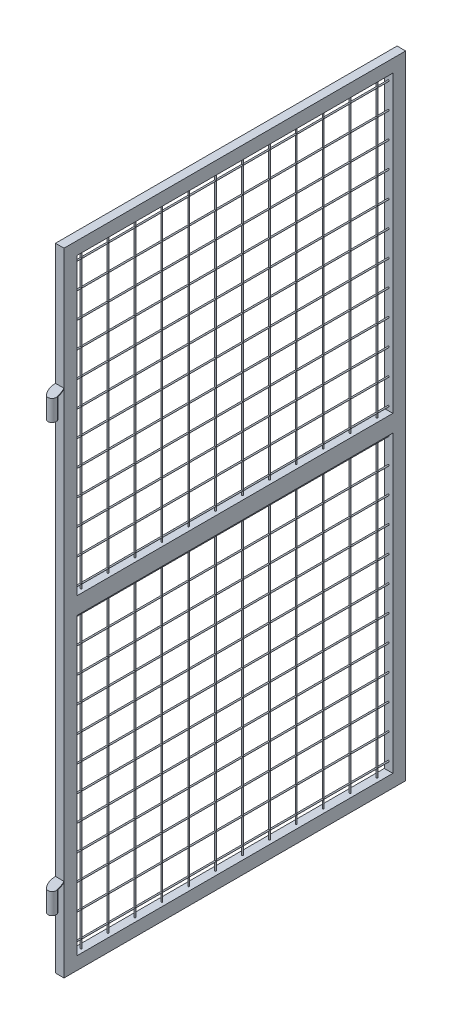
SolidWorks part; units mm, degrees
material "1.0570 (S355J2G3)"
ref_plane "Top Plane" through (0, 0, 0) normal (0, 0, 1) x (1, 0, 0)
ref_plane "Right Plane" through (0, 0, 0) normal (0, 1, 0) x (1, 0, 0)
ref_plane "Front Plane" through (0, 0, 0) normal (1, 0, 0) x (0, 0, -1)
sketch "Sketch1" plane through (0, 0, 0) normal (1, 0, 0) x (0, 0, -1)
  line L0 (30, 1450) -> (770, 1450)
  line L1 (0, 0) -> (800, 0)
  line L2 (0, 0) -> (0, 1480)
  line L3 (0, 1480) -> (800, 1480)
  line L4 (800, 0) -> (800, 1480)
  line L5 (770, 30) -> (770, 720)
  line L6 (30, 30) -> (770, 30)
  line L7 (30, 30) -> (30, 720)
  line L8 (30, 740) -> (810, 740) construction
  line L9 (30, 720) -> (770, 720)
  line L10 (30, 760) -> (770, 760)
  line L11 (0, 760) -> (840, 760) construction
  line L12 (0, 740) -> (840, 740) construction
  line L13 (0, 720) -> (840, 720) construction
  line L14 (30, 760) -> (30, 1450)
  line L15 (30, 30) -> (30, 1450) construction
  line L16 (770, 760) -> (770, 1450)
  line L17 (770, 30) -> (770, 1450) construction
  dimension "D1" = 1480
  dimension "D2" = 800
  dimension "D3" = 30
  dimension "D4" = 20
  dimension "D5" = 20
extrude "Boss-Extrude1" add sketch "Sketch1" along normal blind 20
ref_plane "Plane1" through (0, 194, 0) normal (0, 1, 0) x (1, 0, 0)
sketch "Sketch2" plane through (0, 194, 0) normal (0, 1, 0) x (1, 0, 0)
  line L0 (0, 0) -> (20, 0)
  circle A0 centre (20.0938, -28.0004) radius 9.5
  arc A1 (12.8279, -34.1205) -> (0, 0) centre (54.5822, 1.0489) cw
  arc A2 (29.3611, -25.9105) -> (20, 0) centre (-78.5176, -50.2393) ccw
  dimension "D1" = 19
extrude "Boss-Extrude2" add sketch "Sketch2" along normal blind 2 contours A0 A2 L0 A1 | A0 region at (12.5489, 194, 11.538) region at (20.0938, 194, 28.0004)
extrude "Boss-Extrude3" add sketch "Sketch2<3>" against normal blind 47 contours A0 region at (20.0938, 194, 28.0004)
sketch "Sketch2<3>" plane through (0, 194, 0) normal (0, 1, 0) x (1, 0, 0) same geometry as "Sketch2"
pattern_linear "LPattern1" count 2 spacing 1000 along (0, 1, 0) of "Boss-Extrude3", "Boss-Extrude2"
sketch "Sketch3" plane through (0, 0, -30) normal (0, 0, -1) x (-1, 0, 0)
  line L0 (-20, 30) -> (0, 30) construction
  line L1 (-20, 720) -> (-20, 30) construction
  circle A0 centre (-10, 50) radius 1.5
  dimension "D1" = 3
  dimension "D2" = 20
  dimension "D3" = 10
extrude "Boss-Extrude4" add sketch "Sketch3" along normal blind 752
pattern_linear "LPattern2" count 24 spacing 60 along (0, 1, 0) of "Boss-Extrude4"
sketch "Sketch4" plane through (0, 30, 0) normal (0, 1, 0) x (1, 0, 0)
  line L0 (20, 30) -> (0, 30) construction
  line L1 (0, 30) -> (0, 770) construction
  circle A0 centre (10, 50) radius 1.5
  dimension "D1" = 3
  dimension "D2" = 20
  dimension "D3" = 10
extrude "Boss-Extrude5" add sketch "Sketch4" along normal blind 1430
pattern_linear "LPattern3" count 12 spacing 63 along (0, 0, -1) of "Boss-Extrude5"
